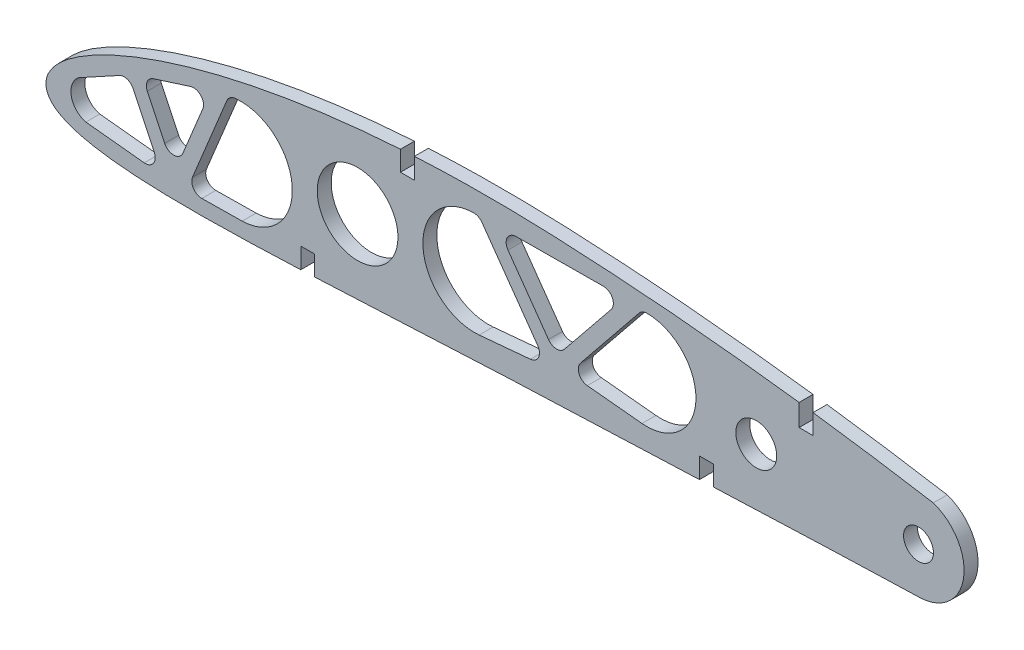
SolidWorks part; units mm, degrees
material "фанера"
ref_plane "Front" through (0, 0, 0) normal (0, 0, 1) x (1, 0, 0)
ref_plane "Top" through (0, 0, 0) normal (0, 1, 0) x (1, 0, 0)
ref_plane "Right" through (0, 0, 0) normal (1, 0, 0) x (0, 0, -1)
curve "Кривая1"
  spline degree 3 poles (0.048, 0.6214, 0) (0.0227, 0.3735, 0) (-0.0278, -0.1225, 0) (0.078, -0.8844, 0) (0.3497, -1.6388, 0) (0.8143, -2.3651, 0) (1.4635, -3.0393, 0) (2.291, -3.661, 0) (3.3059, -4.2358, 0) (4.5353, -4.7737, 0) (6.0297, -5.2822, 0) (7.869, -5.7653, 0) (10.1688, -6.2217, 0) (13.0754, -6.6396, 0) (16.7281, -6.993, 0) (21.19, -7.2473, 0) (26.4, -7.3766, 0) (32.1974, -7.3763, 0) (38.3978, -7.2614, 0) (44.8576, -7.0566, 0) (51.4865, -6.7865, 0) (58.231, -6.4723, 0) (65.0521, -6.1329, 0) (71.9108, -5.784, 0) (78.7714, -5.4397, 0) (85.6105, -5.111, 0) (92.4321, -4.805, 0) (99.255, -4.532, 0) (106.0974, -4.2783, 0) (112.9692, -4.0031, 0) (119.8644, -3.7232, 0) (126.7739, -3.4401, 0) (133.6816, -3.1587, 0) (140.5819, -2.8824, 0) (147.472, -2.6139, 0) (154.3526, -2.3556, 0) (161.225, -2.1094, 0) (168.0909, -1.8766, 0) (174.9516, -1.6586, 0) (181.8086, -1.4564, 0) (188.6632, -1.2704, 0) (195.5166, -1.1011, 0) (202.3695, -0.9486, 0) (209.2212, -0.8129, 0) (216.0668, -0.6936, 0) (222.8864, -0.5903, 0) (229.6176, -0.5029, 0) (236.0874, -0.4315, 0) (241.9808, -0.3765, 0) (246.559, -0.3395, 0) (249.1205, -0.3213, 0) (250, -0.315, 0) knots 0 0 0 0 0.002941 0.005884 0.009016 0.012365 0.016008 0.020037 0.024574 0.029784 0.035897 0.04324 0.052276 0.063635 0.077983 0.095698 0.11652 0.139661 0.164312 0.189919 0.216157 0.242838 0.269834 0.296993 0.324123 0.351139 0.378036 0.404946 0.431961 0.459078 0.486347 0.513641 0.540929 0.568176 0.59538 0.622543 0.649673 0.676775 0.703855 0.730919 0.757971 0.785018 0.812062 0.839103 0.866132 0.893099 0.919831 0.94581 0.969681 0.98959 1 1 1 1
curve "Кривая2"
  spline degree 3 poles (250, 0.315, 0) (249.1557, 0.545, 0) (246.7202, 1.2085, 0) (242.3913, 2.3583, 0) (236.8498, 3.7876, 0) (230.7799, 5.298, 0) (224.4559, 6.8129, 0) (218.0305, 8.2916, 0) (211.5624, 9.7197, 0) (205.0724, 11.0924, 0) (198.568, 12.4079, 0) (192.0524, 13.6653, 0) (185.5276, 14.8641, 0) (178.9953, 16.0034, 0) (172.4571, 17.0824, 0) (165.9143, 18.0998, 0) (159.3687, 19.0545, 0) (152.8218, 19.9449, 0) (146.2754, 20.7693, 0) (139.7314, 21.5257, 0) (133.1918, 22.212, 0) (126.6587, 22.8257, 0) (120.1368, 23.364, 0) (113.6286, 23.8247, 0) (107.1527, 24.2002, 0) (100.7411, 24.4984, 0) (94.4118, 24.6866, 0) (88.1559, 24.7401, 0) (81.949, 24.6588, 0) (75.7805, 24.441, 0) (69.6537, 24.0819, 0) (63.5754, 23.578, 0) (57.5552, 22.9249, 0) (51.6058, 22.1191, 0) (45.7444, 21.1566, 0) (39.9959, 20.0354, 0) (34.3979, 18.7563, 0) (29.0104, 17.3276, 0) (23.9258, 15.7719, 0) (19.2707, 14.1343, 0) (15.1791, 12.4833, 0) (11.7405, 10.8956, 0) (8.9594, 9.4296, 0) (6.7609, 8.1086, 0) (5.0337, 6.9246, 0) (3.6717, 5.8542, 0) (2.5921, 4.8713, 0) (1.7382, 3.9526, 0) (1.0699, 3.0809, 0) (0.5716, 2.2416, 0) (0.2158, 1.4308, 0) (0.1023, 0.8832, 0) (0.048, 0.6214, 0) knots 0 0 0 0 0.010162 0.029313 0.052012 0.076619 0.101948 0.127526 0.153184 0.178868 0.204558 0.230246 0.255926 0.281594 0.307246 0.332878 0.358485 0.384061 0.409603 0.435104 0.460559 0.485959 0.511303 0.536552 0.561723 0.586629 0.611085 0.635251 0.659272 0.683164 0.706922 0.730536 0.753983 0.777235 0.800246 0.822951 0.845237 0.866916 0.887662 0.906968 0.924203 0.938879 0.950932 0.960693 0.968647 0.975233 0.980795 0.985584 0.989782 0.993521 0.996902 1 1 1 1
sketch "Эскиз2" plane through (0, 0, 0) normal (0, 0, 1) x (1, 0, 0)
  line L0 (-1.2592, 0) -> (250.7702, 0) construction
  line L1 (250.1305, 0) -> (250.1305, 80.0888) construction
  line L2 (0, 0) -> (0, 69.7453) construction
  line L3 (62.5326, 123.1249) -> (62.5326, -48.5934) construction
  line L4 (142.5326, 131.1199) -> (142.5326, -55.0117) construction
  line L5 (62.5326, 8.5962) -> (142.5326, 8.5962) construction
  line L6 (62.5326, 8.5962) -> (150.6431, 8.5962) construction
  line L7 (175.0913, 92.567) -> (175.0913, -39.4544) construction
  line L8 (165.9405, 18.0854) -> (165.9405, -1.9504)
  line L9 (87.4969, 19.5968) -> (98.657, 3.8464)
  line L12 (107.2666, 5.069) -> (119.0427, 19.6405)
  line L13 (92.7103, 17.4282) -> (100.8475, 5.9439)
  line L14 (104.0349, 5.843) -> (113.4136, 17.4479)
  line L15 (108.6238, 1.8217) -> (119.6039, 0.7278)
  line L16 (94.3284, 20.5844) -> (111.8443, 20.705)
  line L17 (86.9285, -0.2347) -> (97.2059, 0.6983)
  line L18 (17.4887, 7.868) -> (21.7254, -1.0733)
  line L19 (29.4016, -1.5679) -> (36.2887, 15.1777)
  line L20 (20.3422, 8.8519) -> (23.813, 1.5271)
  line L21 (27.4701, 1.6228) -> (31.461, 11.3265)
  line L22 (7.9994, -2.6904) -> (19.7094, -3.9188)
  line L23 (31.2779, -4.3285) -> (39.3668, -4.221)
  line L24 (6.5801, 4.311) -> (14.7212, 8.7661)
  line L25 (21.5421, 11.6138) -> (29.0038, 13.9928)
  line L26 (72.5326, 27.406) -> (72.5326, 20.4403) construction
  line L27 (52.5326, -12.1202) -> (52.5326, -2.6904) construction
  line L28 (152.5326, 24.4982) -> (152.5326, 15.921) construction
  line L29 (132.5326, -7.5811) -> (132.5326, 3.1811) construction
  line L30 (151.1326, 20.1529) -> (151.1326, 15.7875)
  line L31 (151.1326, 15.7875) -> (153.9326, 15.7875)
  line L32 (153.9326, 15.7875) -> (153.9326, 19.7875)
  line L33 (131.1326, -3.2627) -> (131.1326, 0.8506)
  line L34 (131.1326, 0.8506) -> (133.9326, 0.8506)
  line L35 (133.9326, 0.8506) -> (133.9326, -3.1494)
  line L36 (71.1326, 24.1575) -> (71.1326, 20.1575)
  line L37 (71.1326, 20.1575) -> (73.9326, 20.1575)
  line L38 (73.9326, 20.1575) -> (73.9326, 24.3239)
  line L39 (51.1326, -6.7954) -> (51.1326, -2.6707)
  line L40 (51.1326, -2.6707) -> (53.9326, -2.6707)
  line L41 (53.9326, -2.6707) -> (53.9326, -6.6707)
  arc A0 (250, 0.315) -> (250, -0.315) centre (249.685, 0) cw
  circle A3 centre (62.5326, 8.5962) radius 8.1
  circle A5 centre (62.5326, 8.5962) radius 80 construction
  circle A6 centre (142.5326, 8.5962) radius 4.1
  arc A7 (175.0913, 16.6448) -> (175.0913, -1.657) centre (175.0913, 7.4939) ccw
  arc A10 (107.2666, 5.069) -> (108.6238, 1.8217) centre (108.8221, 3.8118) ccw
  arc A11 (85.8347, 20.4403) -> (86.9285, -0.2347) centre (85.9919, 10.0822) ccw
  arc A12 (120.6027, 20.3833) -> (119.6039, 0.7278) centre (120.5806, 10.5313) cw
  arc A13 (120.6027, 20.3833) -> (119.0427, 19.6405) centre (120.5982, 18.3834) ccw
  arc A14 (85.8347, 20.4403) -> (87.4969, 19.5968) centre (85.8651, 18.4406) cw
  arc A15 (100.8475, 5.9439) -> (104.0349, 5.843) centre (102.4794, 7.1001) ccw
  arc A16 (37.9117, 16.4041) -> (36.2887, 15.1777) centre (38.1384, 14.417) ccw
  arc A17 (98.657, 3.8464) -> (97.2059, 0.6983) centre (97.0251, 2.6901) cw
  arc A18 (92.7103, 17.4282) -> (94.3284, 20.5844) centre (94.3421, 18.5845) cw
  arc A19 (113.4136, 17.4479) -> (111.8443, 20.705) centre (111.8581, 18.7051) ccw
  arc A20 (6.5801, 4.311) -> (7.9994, -2.6904) centre (8.9558, 1.1481) ccw
  arc A21 (37.9117, 16.4041) -> (39.3668, -4.221) centre (39.0848, 6.123) cw
  arc A22 (23.813, 1.5271) -> (27.4701, 1.6228) centre (25.6204, 2.3835) ccw
  arc A23 (31.461, 11.3265) -> (29.0038, 13.9928) centre (29.6113, 12.0873) ccw
  arc A24 (20.3422, 8.8519) -> (21.5421, 11.6138) centre (22.1496, 9.7083) cw
  arc A25 (17.4887, 7.868) -> (14.7212, 8.7661) centre (15.6813, 7.0116) ccw
  arc A26 (19.7094, -3.9188) -> (21.7254, -1.0733) centre (19.9181, -1.9297) ccw
  arc A27 (29.4016, -1.5679) -> (31.2779, -4.3285) centre (31.2513, -2.3286) ccw
  circle A28 centre (175.0913, 7.4939) radius 3
  circle A29 centre (175.0913, 7.4939) radius 9.1509
  spline S0 degree 3 poles (250, 0.315) (249.1557, 0.545) (246.7202, 1.2085) (242.3913, 2.3583) (236.8498, 3.7876) (230.7799, 5.298) (224.4559, 6.8129) (218.0305, 8.2916) (211.5624, 9.7197) (205.0724, 11.0924) (198.568, 12.4079) (192.0524, 13.6653) (185.5276, 14.8641) (178.9953, 16.0034) (172.4571, 17.0824) (165.9143, 18.0998) (159.3687, 19.0545) (152.8218, 19.9449) (146.2754, 20.7693) (139.7314, 21.5257) (133.1918, 22.212) (126.6587, 22.8257) (120.1368, 23.364) (113.6286, 23.8247) (107.1527, 24.2002) (100.7411, 24.4984) (94.4118, 24.6866) (88.1559, 24.7401) (81.949, 24.6588) (75.7805, 24.441) (69.6537, 24.0819) (63.5754, 23.578) (57.5552, 22.9249) (51.6058, 22.1191) (45.7444, 21.1566) (39.9959, 20.0354) (34.3979, 18.7563) (29.0104, 17.3276) (23.9258, 15.7719) (19.2707, 14.1343) (15.1791, 12.4833) (11.7405, 10.8956) (8.9594, 9.4296) (6.7609, 8.1086) (5.0337, 6.9246) (3.6717, 5.8542) (2.5921, 4.8713) (1.7382, 3.9526) (1.0699, 3.0809) (0.5716, 2.2416) (0.2158, 1.4308) (0.1023, 0.8832) (0.048, 0.6214) knots 0 0 0 0 0.010162 0.029313 0.052012 0.076619 0.101948 0.127526 0.153184 0.178868 0.204558 0.230246 0.255926 0.281594 0.307246 0.332878 0.358485 0.384061 0.409603 0.435104 0.460559 0.485959 0.511303 0.536552 0.561723 0.586629 0.611085 0.635251 0.659272 0.683164 0.706922 0.730536 0.753983 0.777235 0.800246 0.822951 0.845237 0.866916 0.887662 0.906968 0.924203 0.938879 0.950932 0.960693 0.968647 0.975233 0.980795 0.985584 0.989782 0.993521 0.996902 1 1 1 1 construction
  spline S1 degree 3 poles (0.048, 0.6214) (0.0227, 0.3735) (-0.0278, -0.1225) (0.078, -0.8844) (0.3497, -1.6388) (0.8143, -2.3651) (1.4635, -3.0393) (2.291, -3.661) (3.3059, -4.2358) (4.5353, -4.7737) (6.0297, -5.2822) (7.869, -5.7653) (10.1688, -6.2217) (13.0754, -6.6396) (16.7281, -6.993) (21.19, -7.2473) (26.4, -7.3766) (32.1974, -7.3763) (38.3978, -7.2614) (44.8576, -7.0566) (51.4865, -6.7865) (58.231, -6.4723) (65.0521, -6.1329) (71.9108, -5.784) (78.7714, -5.4397) (85.6105, -5.111) (92.4321, -4.805) (99.255, -4.532) (106.0974, -4.2783) (112.9692, -4.0031) (119.8644, -3.7232) (126.7739, -3.4401) (133.6816, -3.1587) (140.5819, -2.8824) (147.472, -2.6139) (154.3526, -2.3556) (161.225, -2.1094) (168.0909, -1.8766) (174.9516, -1.6586) (181.8086, -1.4564) (188.6632, -1.2704) (195.5166, -1.1011) (202.3695, -0.9486) (211.4992, -0.7677) (220.6031, -0.6199) (229.6176, -0.5029) (236.0874, -0.4315) (241.9808, -0.3765) (246.559, -0.3395) (249.1205, -0.3213) (250, -0.315) knots 0 0 0 0 0.002941 0.005884 0.009016 0.012365 0.016008 0.020037 0.024574 0.029784 0.035897 0.04324 0.052276 0.063635 0.077983 0.095698 0.11652 0.139661 0.164312 0.189919 0.216157 0.242838 0.269834 0.296993 0.324123 0.351139 0.378036 0.404946 0.431961 0.459078 0.486347 0.513641 0.540929 0.568176 0.59538 0.622543 0.649673 0.676775 0.703855 0.730919 0.757971 0.785018 0.812062 0.839103 0.893099 0.919831 0.94581 0.969681 0.98959 1 1 1 1 construction
  spline S2 degree 3 poles (250, 0.315) (249.1557, 0.545) (246.7202, 1.2085) (242.3913, 2.3583) (236.8498, 3.7876) (230.7799, 5.298) (224.4559, 6.8129) (218.0305, 8.2916) (211.5624, 9.7197) (205.0724, 11.0924) (198.568, 12.4079) (192.0524, 13.6653) (185.5276, 14.8641) (178.9953, 16.0034) (172.4571, 17.0824) (165.9143, 18.0998) (159.7397, 19.0004) (155.7443, 19.5471) (153.9326, 19.7875) knots 0 0 0 0 0.010162 0.029313 0.052012 0.076619 0.101948 0.127526 0.153184 0.178868 0.204558 0.230246 0.255926 0.281594 0.307246 0.332878 0.358485 0.379707 0.379707 0.379707 0.379707
  spline S3 degree 3 poles (0.048, 0.6214) (0.0227, 0.3735) (-0.0278, -0.1225) (0.078, -0.8844) (0.3497, -1.6388) (0.8143, -2.3651) (1.4635, -3.0393) (2.291, -3.661) (3.3059, -4.2358) (4.5353, -4.7737) (6.0297, -5.2822) (7.869, -5.7653) (10.1688, -6.2217) (13.0754, -6.6396) (16.7281, -6.993) (21.19, -7.2473) (26.4, -7.3766) (32.1974, -7.3763) (38.3978, -7.2614) (44.7521, -7.06) (49.0233, -6.8868) (51.1326, -6.7954) knots 0 0 0 0 0.002941 0.005884 0.009016 0.012365 0.016008 0.020037 0.024574 0.029784 0.035897 0.04324 0.052276 0.063635 0.077983 0.095698 0.11652 0.139661 0.164312 0.189919 0.214908 0.214908 0.214908 0.214908
  spline S4 degree 3 poles (151.1326, 20.1529) (149.5127, 20.3609) (145.7129, 20.8343) (139.7314, 21.5257) (133.1918, 22.212) (126.6587, 22.8257) (120.1368, 23.364) (113.6286, 23.8247) (107.1527, 24.2002) (100.7411, 24.4984) (94.4118, 24.6866) (88.1559, 24.7401) (81.949, 24.6588) (77.2124, 24.4916) (74.545, 24.3569) (73.9326, 24.3239) knots 0.390637 0.390637 0.390637 0.390637 0.409603 0.435104 0.460559 0.485959 0.511303 0.536552 0.561723 0.586629 0.611085 0.635251 0.659272 0.683164 0.690286 0.690286 0.690286 0.690286
  spline S5 degree 3 poles (133.9326, -3.1494) (136.1503, -3.0598) (140.6644, -2.8792) (147.472, -2.6139) (154.3526, -2.3556) (161.225, -2.1094) (168.0909, -1.8766) (174.9516, -1.6586) (181.8086, -1.4564) (188.6632, -1.2704) (195.5166, -1.1011) (202.3695, -0.9486) (211.4992, -0.7677) (220.6031, -0.6199) (229.6176, -0.5029) (236.0874, -0.4315) (241.9808, -0.3765) (246.559, -0.3395) (249.1205, -0.3213) (250, -0.315) knots 0.541906 0.541906 0.541906 0.541906 0.568176 0.59538 0.622543 0.649673 0.676775 0.703855 0.730919 0.757971 0.785018 0.812062 0.839103 0.893099 0.919831 0.94581 0.969681 0.98959 1 1 1 1
  spline S6 degree 3 poles (71.1326, 24.1575) (70.636, 24.1252) (68.1106, 23.954) (63.5754, 23.578) (57.5552, 22.9249) (51.6058, 22.1191) (45.7444, 21.1566) (39.9959, 20.0354) (34.3979, 18.7563) (29.0104, 17.3276) (23.9258, 15.7719) (19.2707, 14.1343) (15.1791, 12.4833) (11.7405, 10.8956) (8.9594, 9.4296) (6.7609, 8.1086) (5.0337, 6.9246) (3.6717, 5.8542) (2.5921, 4.8713) (1.7382, 3.9526) (1.0699, 3.0809) (0.5716, 2.2416) (0.2158, 1.4308) (0.1023, 0.8832) (0.048, 0.6214) knots 0.701143 0.701143 0.701143 0.701143 0.706922 0.730536 0.753983 0.777235 0.800246 0.822951 0.845237 0.866916 0.887662 0.906968 0.924203 0.938879 0.950932 0.960693 0.968647 0.975233 0.980795 0.985584 0.989782 0.993521 0.996902 1 1 1 1
  spline S7 degree 3 poles (53.9326, -6.6707) (55.3566, -6.6057) (59.0587, -6.4311) (65.0521, -6.1329) (71.9108, -5.784) (78.7714, -5.4397) (85.6105, -5.111) (92.4321, -4.805) (99.255, -4.532) (106.0974, -4.2783) (112.9692, -4.0031) (119.8644, -3.7232) (125.9231, -3.4749) (129.6799, -3.3217) (131.1326, -3.2627) knots 0.225966 0.225966 0.225966 0.225966 0.242838 0.269834 0.296993 0.324123 0.351139 0.378036 0.404946 0.431961 0.459078 0.486347 0.513641 0.53085 0.53085 0.53085 0.53085
  point P15 (62.5326, 0)
  point P16 (142.5326, 0)
  point P21 (62.5326, 23.4501)
  point P22 (62.5326, -6.2577)
  point P26 (175.0913, 16.6448)
  point P28 (175.0913, -1.657)
  point P52 (119.6039, 20.3348)
  point P55 (86.9285, 20.3991)
  point P58 (102.3746, 3.7886)
  point P65 (100.665, 1.0123)
  point P86 (25.7497, -2.5601)
  point P88 (23.2497, -4.2901)
  point P91 (28.2497, -4.3687)
  dimension "D1" = 0.4455
  dimension "D6" = 16.2
  dimension "D7" = 160
  dimension "D9" = 8.2
  dimension "D12" = 9.1509
  dimension "D21" = 2
  dimension "D22" = 2
  dimension "D23" = 2
  dimension "D19" = 2
  dimension "D29" = 2
  dimension "D14" = 2
  dimension "D30" = 6
  dimension "D2" = 250.1305
  dimension "D3" = 62.5326
  dimension "D4" = 80
  dimension "D5" = 29.7079
  dimension "D8" = 14.8539
  dimension "D10" = 0
  dimension "D11" = 175.0913
  dimension "D13" = 67.8
  dimension "D15" = 5
  dimension "D16" = 8
  dimension "D17" = 3
  dimension "D18" = 3
  dimension "D20" = 5
  dimension "D24" = 5
  dimension "D25" = 3
  dimension "D26" = 3
  dimension "D27" = 5
  dimension "D28" = 2.5
  dimension "D31" = 10
  dimension "D32" = 10
  dimension "D33" = 10
  dimension "D34" = 10
  dimension "D35" = 2.8
  dimension "D36" = 1.4
  dimension "D37" = 4
  dimension "D38" = 2.8
  dimension "D39" = 1.4
  dimension "D40" = 4
  dimension "D41" = 2.8
  dimension "D42" = 1.4
  dimension "D43" = 4
  dimension "D44" = 1.4
  dimension "D45" = 2.8
  dimension "D46" = 4
extrude "Бобышка-Вытянуть2" add sketch "Эскиз2" along normal mid plane 2.8 contours S2 S3 L8 L20 A24 L25 A23 L21 A22 L9 A17 L17 A11 A14 A3 A6 A13 A12 L15 A10 L12 A19 L14 A15 L13 A18 L16 A26 L22 A20 L24 A25 L18 A27 L19 A16 A21 L23 | A7 S2 L8 | L8 S5 A7 | A7 S5 A29 S2 A28 region at (168.2631, 15.2861, 0) region at (164.2503, 12.7896, 0) region at (168.0518, 0.2403, 0) region at (168.8037, 13.7815, 0)
equation "\"D3@Эскиз2\"=\"D2@Эскиз2\"/4"
equation "\"D8@Эскиз2\"=\"D5@Эскиз2\"/2"
equation "\"D7@Эскиз2\"=\"D4@Эскиз2\"*2"
equation "\"D11@Эскиз2\"=\"D2@Эскиз2\"*0.7"
equation "\"D28@Эскиз2\"=\"D27@Эскиз2\"/2"
